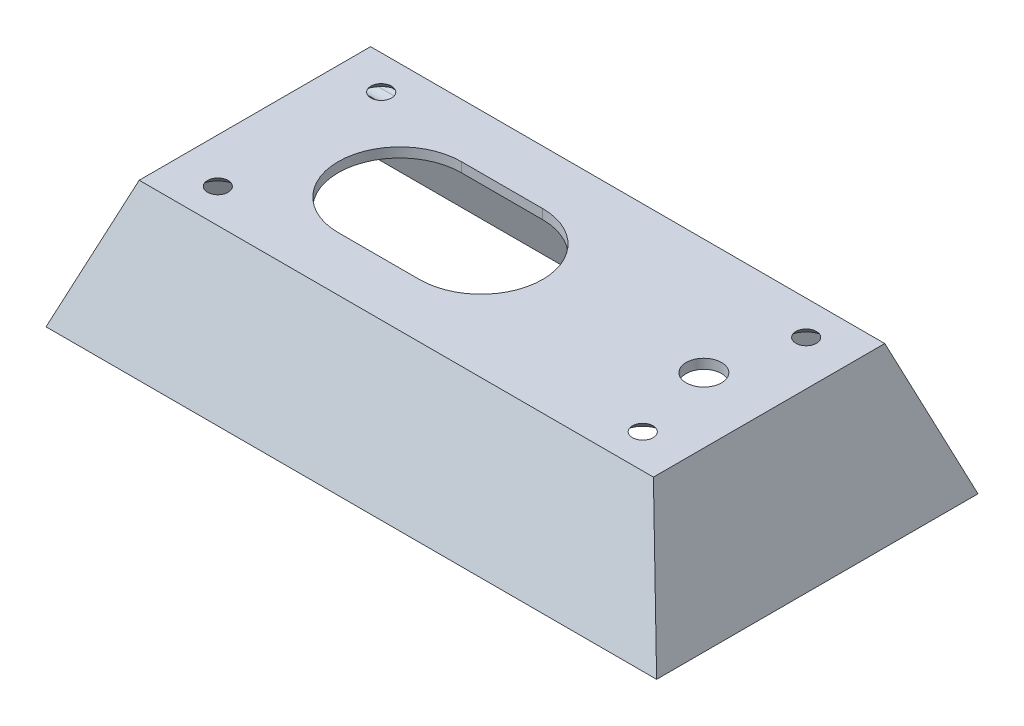
SolidWorks part; units mm, degrees
ref_plane "Ön Düzlem" through (0, 0, 0) normal (0, 0, 1) x (1, 0, 0)
ref_plane "Üst Düzlem" through (0, 0, 0) normal (0, 1, 0) x (1, 0, 0)
ref_plane "Sağ Düzlem" through (0, 0, 0) normal (1, 0, 0) x (0, 0, -1)
sketch "Çizim1" plane through (0, 0, 0) normal (0, 1, 0) x (1, 0, 0)
  line L5 (-47.5, 25) -> (47.5, 25)
  line L6 (-47.5, 25) -> (-47.5, -25)
  line L7 (-47.5, -25) -> (47.5, -25)
  line L8 (47.5, 25) -> (47.5, -25)
  line L9 (-47.5, 25) -> (47.5, -25) construction
  line L10 (-47.5, -25) -> (47.5, 25) construction
  point P0 (0, 0)
  dimension "D1" = 50
  dimension "D2" = 95
ref_plane "Düzlem2" through (0, 20, 0) normal (0, 1, 0) x (1, 0, 0)
sketch "Çizim3" plane through (0, 20, 0) normal (0, 1, 0) x (1, 0, 0)
  line L5 (-40, 18) -> (40, 18)
  line L6 (-40, 18) -> (-40, -18)
  line L7 (-40, -18) -> (40, -18)
  line L8 (40, 18) -> (40, -18)
  line L9 (-40, 18) -> (40, -18) construction
  line L10 (-40, -18) -> (40, 18) construction
  point P0 (0, 0)
  point P5 (0, 0)
  dimension "D1" = 36
  dimension "D2" = 80
loft "Loft4" add profiles "Çizim3", "Çizim1" connector at (40, 20, 18) connector at (47.5, 0, 25)
shell "İç Boşaltma1" thickness 1.5 removed face at (0, 0, 0)
sketch "Çizim4" plane through (0, 20, 0) normal (0, 1, 0) x (1, 0, 0)
  line L0 (-17.4598, 0) -> (-4.8148, 0) construction
  line L1 (-17.4598, 9.5726) -> (-4.8148, 9.5726)
  line L2 (-17.4598, -9.5726) -> (-4.8148, -9.5726)
  arc A0 (-17.4598, 9.5726) -> (-17.4598, -9.5726) centre (-17.4598, 0) ccw
  arc A1 (-4.8148, -9.5726) -> (-4.8148, 9.5726) centre (-4.8148, 0) ccw
  point P2 (-11.1373, 0)
extrude "Kes-Ekstrüzyon1" cut sketch "Çizim4" against normal blind 2
sketch "Çizim5" plane through (0, 7.2996, -20.8559) normal (0, -0.3304, 0.9439) x (1, 0, 0)
  line L0 (-38.9605, 11.8666) -> (-45.898, -7.7338) construction
  line L1 (-39.7392, 9.6666) -> (-21.1173, 9.6666)
  line L3 (-40.2701, 8.1666) -> (-21.1173, 8.1666)
  line L4 (-21.1173, 9.6666) -> (-21.1173, 8.1666)
  line L5 (-40.2701, 8.1666) -> (-39.7392, 9.6666)
  line L6 (-39.7392, 9.6666) -> (-40.2701, 8.1666)
  line L7 (38.9605, 11.8666) -> (-38.9605, 11.8666) construction
  line M7 (-38.9605, 11.8666) -> (-45.898, -7.7338)
  dimension "D1" = 1.5
  dimension "D2" = 2.2
extrude "Yükseklik-Ekstrüzyon4" add sketch "Çizim5" along normal blind 2 contours L4 L1 L3 M7 region at (-30.5616, 15.7123, -17.9115)
fillet "Radyus1" radius 1.3 2 edges at (-30.6937, 14.347, -16.2704) (-30.4282, 15.7628, -15.7748) tangent propagation no
sketch "Çizim6" plane through (0, 7.2996, 20.8559) normal (0, -0.3304, -0.9439) x (-1, 0, 0)
  line L0 (38.9605, 11.8666) -> (45.898, -7.7338) construction
  line L1 (39.7392, 9.6666) -> (-7.6053, 9.6666)
  line L3 (40.4471, 7.6666) -> (-7.6053, 7.6666)
  line L4 (-7.6053, 9.6666) -> (-7.6053, 7.6666)
  line L5 (39.7392, 9.6666) -> (40.4471, 7.6666)
  line L6 (38.9605, 11.8666) -> (-38.9605, 11.8666) construction
  dimension "D1" = 2.2
  dimension "D2" = 2
extrude "Yükseklik-Ekstrüzyon5" add sketch "Çizim6" along normal blind 1.5
fillet "Radyus2" radius 1 2 edges at (-16.4209, 14.0403, 16.9075) (-16.067, 15.928, 16.2468)
sketch "Çizim7" plane through (0, 20, 0) normal (0, 1, 0) x (1, 0, 0)
  circle A0 centre (29.8502, 0) radius 2.75
  dimension "D1" = 5.5
extrude "Kes-Ekstrüzyon2" cut sketch "Çizim7" against normal blind 10
sketch "Çizim8" plane through (0, 20, 0) normal (0, 1, 0) x (1, 0, 0)
  line L1 (-33.0577, 12.7118) -> (33.0577, 12.7118) construction
  line L2 (-33.0577, 12.7118) -> (-33.0577, -12.7118) construction
  line L3 (-33.0577, -12.7118) -> (33.0577, -12.7118) construction
  line L4 (33.0577, 12.7118) -> (33.0577, -12.7118) construction
  line L5 (-33.0577, 12.7118) -> (33.0577, -12.7118) construction
  line L6 (-33.0577, -12.7118) -> (33.0577, 12.7118) construction
  circle A0 centre (-33.0577, 12.7118) radius 1.5
  circle A1 centre (33.0577, 12.7118) radius 1.5
  circle A2 centre (33.0577, -12.7118) radius 1.5
  circle A3 centre (-33.0577, -12.7118) radius 1.5
  point P0 (0, 0)
  dimension "D1" = 3
extrude "Kes-Ekstrüzyon3" cut sketch "Çizim8" against normal blind 10
chamfer "Pah1" distance 1.6 angle 46 4 edges at (33.0577, 18.5, -11.2118) (-33.0577, 18.5, -11.2118) (33.0577, 18.5, 14.2118) (-33.0577, 18.5, 14.2118) first distance on face at (33.0577, 20, -11.2118) first distance on face at (-33.0577, 20, -11.2118) first distance on face at (33.0577, 20, 14.2118) first distance on face at (-33.0577, 20, 14.2118)
